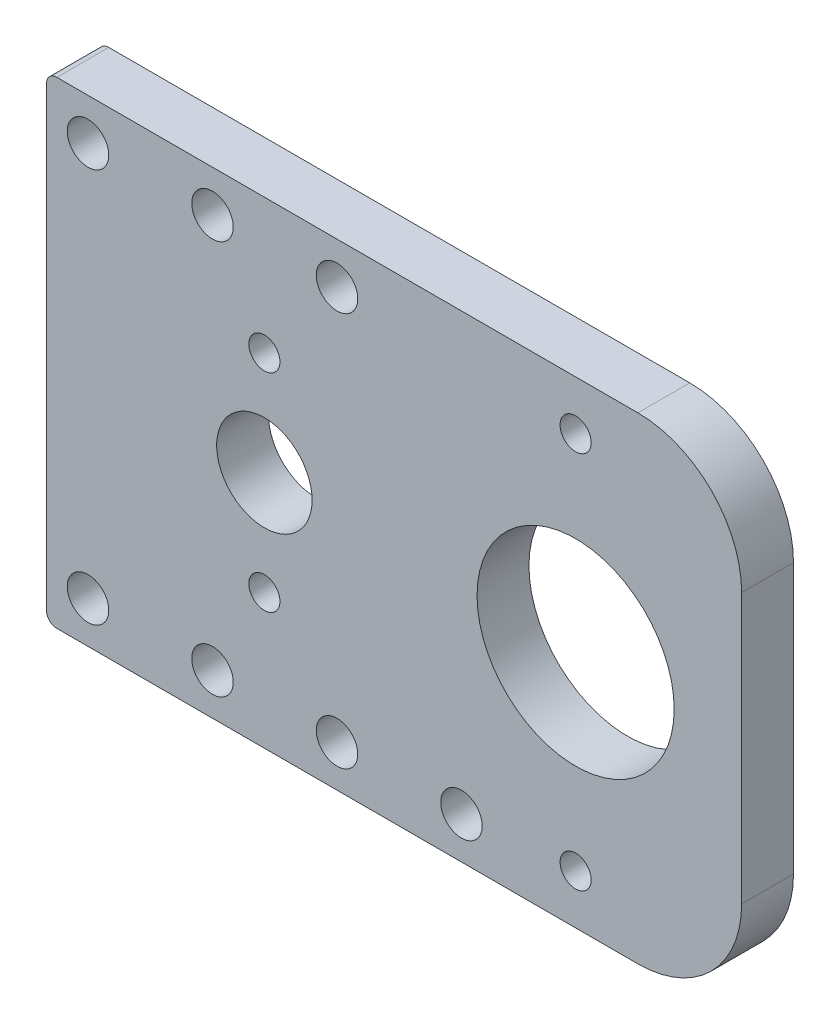
SolidWorks part; units mm, degrees
material "Acrylic (Medium-high impact)"
ref_plane "Front Plane" through (0, 0, 0) normal (0, 0, 1) x (1, 0, 0)
ref_plane "Top Plane" through (0, 0, 0) normal (0, 1, 0) x (1, 0, 0)
ref_plane "Right Plane" through (0, 0, 0) normal (1, 0, 0) x (0, 0, -1)
sketch "Sketch1" plane through (0, 0, 0) normal (0, 0, 1) x (1, 0, 0)
  line L0 (-25.3491, 0) -> (24.7222, 0) construction
  line L1 (40, -23) -> (-40, -23)
  line L2 (40, -23) -> (40, 23)
  line L3 (40, 23) -> (-40, 23)
  line L4 (-40, -23) -> (-40, 23)
  line L5 (40, -23) -> (-40, 23) construction
  line L6 (40, 23) -> (-40, -23) construction
  line L7 (30, 0) -> (30, 18.25)
  line L8 (-40, 23) -> (-25, 23)
  line L9 (-25, 23) -> (-25, -23)
  line L10 (0, 0) -> (0, -10)
  circle A0 centre (0, 0) radius 4.6
  circle A1 centre (30, 0) radius 9.5
  circle A2 centre (30, 18.25) radius 1.5
  circle A3 centre (30, -18.25) radius 1.5
  circle A4 centre (0, -10) radius 1.5
  circle A5 centre (0, 10) radius 1.5
  point P0 (0, 0)
  dimension "D1" = 9.2
  dimension "D2" = 19
  dimension "D7" = 3
  dimension "D10" = 3
  dimension "D3" = 46
  dimension "D4" = 30
  dimension "D5" = 80
  dimension "D6" = 18.25
  dimension "D8" = 15
  dimension "D9" = 10
extrude "Boss-Extrude1" add sketch "Sketch1" along normal blind 5 contours L4 L1 L2 L3 A0 A2 A1 A3 region at (5.1671, 0, 0)
sketch "Sketch2" plane through (0, 0, 5) normal (0, 0, 1) x (1, 0, 0)
  line L0 (-25, -23) -> (-25, 23)
  line L1 (-25, -23) -> (-5, -23)
  line L2 (-25, 23) -> (-5, 23)
  line L3 (-5, -23) -> (-5, 23)
  line L4 (-25, 23) -> (-25, -23)
  line L5 (-25, -23) -> (40, -23)
  line L6 (40, -23) -> (40, 23)
  line L7 (40, 23) -> (-25, 23)
  line L9 (-25, -23) -> (40, -23)
  line L10 (40, -23) -> (40, 23)
  line L11 (40, 23) -> (-25, 23)
  line L12 (-17, 19) -> (-25, 19)
  line L13 (-17, 19) -> (-5, 19)
  line L14 (-5, 19) -> (7, 19)
  line L15 (7, -19) -> (19, -19)
  line L16 (-5, 0) -> (-25, 0)
  line L20 (-25, 23) -> (-25, -23)
  circle A0 centre (-17, 19) radius 2
  circle A1 centre (-5, 19) radius 2
  circle A5 centre (7, 19) radius 2
  circle A6 centre (7, -19) radius 2
  circle A7 centre (-5, -19) radius 2
  circle A8 centre (-17, -19) radius 2
  circle A9 centre (19, -19) radius 2
  dimension "D5" = 4
  dimension "D6" = 4
  dimension "D7" = 19
  dimension "D8" = 4
  dimension "D10" = 4
  dimension "D2" = 20
  dimension "D3" = 12
  dimension "D4" = 12
  dimension "D9" = 8
  dimension "D11" = 12
  dimension "D1" = 0
extrude "Cut-Extrude1" cut sketch "Sketch2" against normal blind 10 contours A8 | A7 L3 | A7 L3 | A6 | A5 | L14 A1 L3 | L3 A1 L13 | L13 A1 L3 | L3 A1 L14 | L13 A0 L12 | L12 A0 L13 region at (7, 20.9434, 5) region at (-5.8488, -19, 5) region at (-4.1512, -19, 5) region at (-17, 19.8488, 5) region at (-17, 18.1512, 5) region at (-5.8488, 18.1512, 5) region at (-4.1512, 18.1512, 5) region at (-5.8488, 19.8488, 5) region at (-4.1512, 19.8488, 5) region at (5.0566, -19, 5) region at (-17, -19, 5)
sketch "Sketch3" plane through (0, 0, 5) normal (0, 0, 1) x (1, 0, 0)
  line L0 (-25, 23) -> (-21, 23)
  line L1 (-21, 23) -> (-21, -23)
  line L4 (40, 23) -> (-25, 23)
  line L5 (-25, 23) -> (-25, -23)
  line L6 (-25, -23) -> (40, -23)
  line L7 (40, -23) -> (40, 23)
  line L8 (40, 23) -> (-25, 23)
  line L9 (-25, 23) -> (-25, -23)
  line L10 (-25, -23) -> (40, -23)
  line L11 (40, -23) -> (40, 23)
  line M10 (40, 23) -> (-25, 23)
  line M11 (-25, 23) -> (-25, -23)
  line M12 (-25, -23) -> (40, -23)
  dimension "D2" = 4
  dimension "D1" = 0
extrude "Cut-Extrude2" cut sketch "Sketch3" against normal through all contours L1 M10 M11 M12 region at (-23, 0, 5)
sketch "Sketch4" plane through (0, 0, 5) normal (0, 0, 1) x (1, 0, 0)
  line L1 (40, 23) -> (46, 23)
  line L2 (40, 23) -> (40, -23)
  line L3 (40, -23) -> (46, -23)
  line L4 (40, 23) -> (-21, 23)
  line L5 (-21, 23) -> (-21, -23)
  line L6 (-21, -23) -> (40, -23)
  line L7 (40, -23) -> (40, 23)
  line L8 (40, 23) -> (-21, 23)
  line L9 (-21, 23) -> (-21, -23)
  line L10 (-21, -23) -> (40, -23)
  line L11 (40, -23) -> (40, 23)
  line L12 (46, 23) -> (46, -23)
  line M19 (40, -23) -> (40, 23)
  dimension "D2" = 6
  dimension "D1" = 0
extrude "Boss-Extrude2" add sketch "Sketch4" against normal up to surface (5 mm away) contours L12 L1 L3 M19 region at (43, 0, 5) up to face at (-15, 19, 0)
fillet "Fillet1" radius 10 2 edges at (46, 23, 2.5) (46, -23, 2.5)
fillet "Fillet2" radius 1 2 edges at (-21, 23, 2.5) (-21, -23, 2.5)
extrude "Cut-Extrude3" cut sketch "Sketch2<3>" against normal blind 10 contours A9 region at (19, -17.0566, 5)
sketch "Sketch2<3>" plane through (0, 0, 5) normal (0, 0, 1) x (1, 0, 0) same geometry as "Sketch2"
